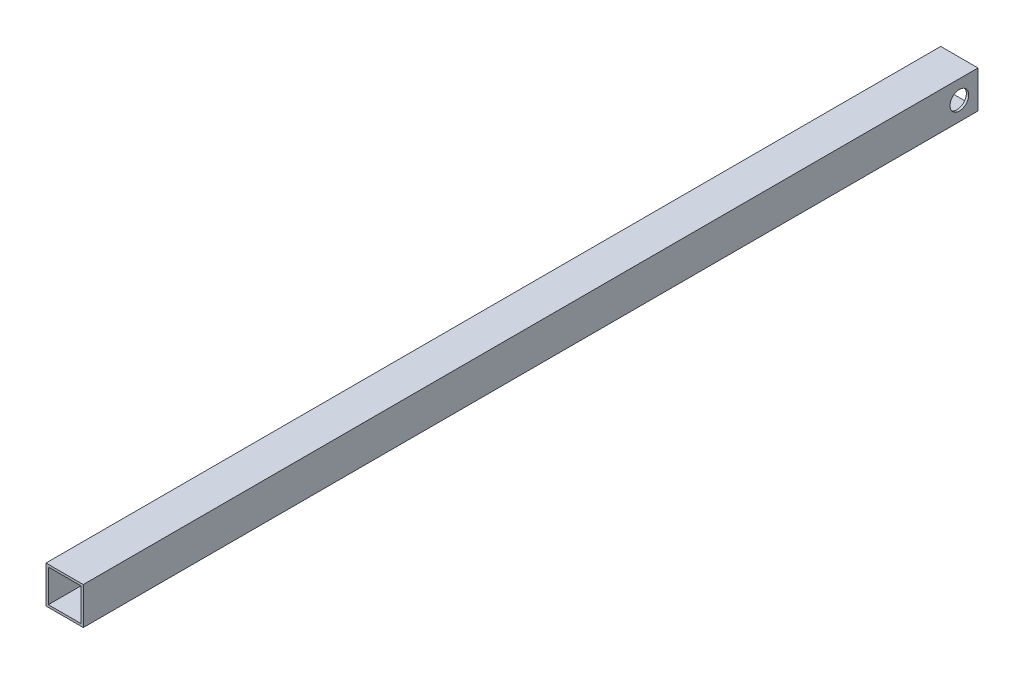
SolidWorks part; units mm, degrees
material "Plain Carbon Steel"
ref_plane "Front Plane" through (0, 0, 0) normal (0, 0, 1) x (1, 0, 0)
ref_plane "Top Plane" through (0, 0, 0) normal (0, 1, 0) x (1, 0, 0)
ref_plane "Right Plane" through (0, 0, 0) normal (1, 0, 0) x (0, 0, -1)
sketch "Sketch2" plane through (0, 0, 0) normal (0, 0, 1) x (1, 0, 0)
  line L0 (0, 12.7) -> (1.5875, 12.7) construction
  line L1 (0, 0) -> (25.4, 0)
  line L2 (0, 0) -> (0, 25.4)
  line L3 (0, 25.4) -> (25.4, 25.4)
  line L4 (25.4, 0) -> (25.4, 25.4)
  line L5 (1.5875, 1.5875) -> (23.8125, 1.5875)
  line L6 (1.5875, 1.5875) -> (1.5875, 23.8125)
  line L7 (1.5875, 23.8125) -> (23.8125, 23.8125)
  line L8 (23.8125, 1.5875) -> (23.8125, 23.8125)
  line L9 (12.7, 23.8125) -> (12.7, 25.4) construction
  line L10 (23.8125, 12.7) -> (25.4, 12.7) construction
  line L11 (12.7, 0) -> (12.7, 1.5875) construction
  dimension "D1" = 25.4
  dimension "D2" = 1.5875
  dimension "D3" = 25.4
extrude "Boss-Extrude1" add sketch "Sketch2" along normal blind 609.6
hole_wizard "1/2 (0.5) Diameter Hole1" positions "Sketch4" profile "Sketch3" hole size "1/2" standard "ANSI Inch" end condition through all
sketch "Sketch4" plane through (0, 0, 0) normal (-1, 0, 0) x (0, 0, 1)
  line L0 (0, 12.7) -> (12.7, 12.7) construction
  line L1 (0, 25.4) -> (0, 0) construction
  point P0 (12.7, 12.7)
  dimension "D1" = 12.7
sketch "Sketch3" plane through (0, 12.7, 12.7) normal (0, 1, 0) x (0, 0, 1)
  line L0 (0, 0) -> (0, 25.4)
  line L1 (0, 25.4) -> (6.35, 25.4)
  line L2 (6.35, 25.4) -> (6.35, 0)
  line L5 (6.35, 0) -> (0, 0)
  line L11 (0, -6.35) -> (0, 107.95) construction
  dimension "Thru Hole Dia." = 12.7
  dimension "Thru Hole Depth" = 25.4
